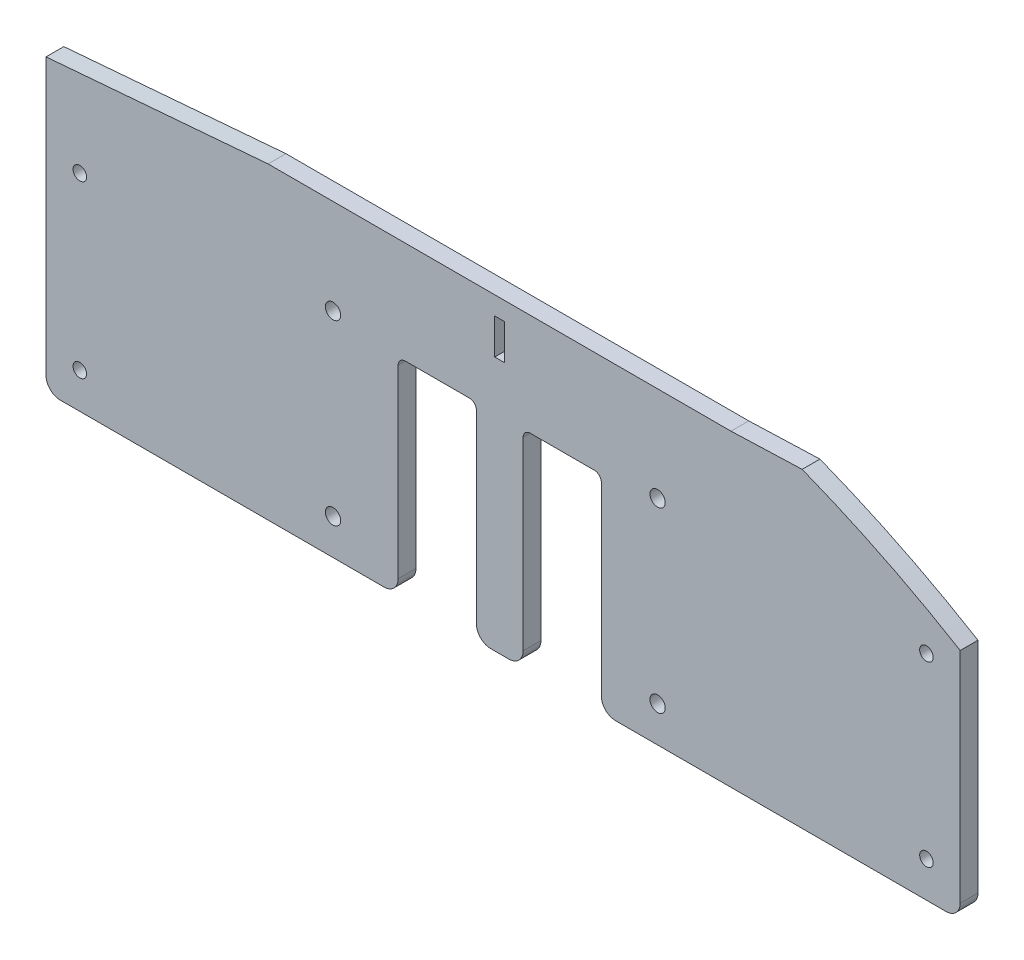
SolidWorks part; units mm, degrees
ref_plane "Front Plane" through (0, 0, 0) normal (0, 0, 1) x (1, 0, 0)
ref_plane "Top Plane" through (0, 0, 0) normal (0, 1, 0) x (1, 0, 0)
ref_plane "Right Plane" through (0, 0, 0) normal (1, 0, 0) x (0, 0, -1)
sketch "Sketch1" plane through (0, 0, 0) normal (0, 0, 1) x (1, 0, 0)
  line L0 (-247.5, -213.0845) -> (-247.5, -198.9021) construction
  line L1 (-243.5, -252.9723) -> (-152.4982, -252.9723)
  line L2 (-247.5, -248.9723) -> (-247.5, -171.4071)
  line L3 (-164.4304, -152.9723) -> (-121.35, -152.9723)
  line L4 (9.5, -248.9723) -> (9.5, -187.4329)
  line L6 (-120, -252.1255) -> (-120, -249.5403) construction
  line L8 (-93.3778, -194.9705) -> (-111.3778, -194.9705)
  line L9 (-91.3778, -196.9705) -> (-91.3778, -248.9723)
  line L11 (-113.3778, -196.9705) -> (-113.3778, -248.9723)
  line L12 (-122.4982, -252.9723) -> (-117.3778, -252.9723)
  line L13 (-128.4982, -194.9705) -> (-146.4982, -194.9705)
  line L14 (-126.4982, -196.9705) -> (-126.4982, -248.9723)
  line L16 (-148.4982, -196.9705) -> (-148.4982, -248.9723)
  line L17 (-87.3778, -252.9723) -> (5.5, -252.9723)
  line L21 (0, -187.4329) -> (0, -185.3896) construction
  line L22 (-105, -258.3454) -> (-105, -242.9215) construction
  line L25 (-118.65, -171.4071) -> (-118.65, -181.4071)
  line L26 (-118.65, -181.4071) -> (-121.35, -181.4071)
  line L27 (-121.35, -181.4071) -> (-121.35, -171.4071)
  line L28 (-121.35, -171.4071) -> (-118.65, -171.4071)
  line L29 (-118.65, -152.9723) -> (-118.65, -162.9723)
  line L30 (-118.65, -162.9723) -> (-121.35, -162.9723)
  line L31 (-121.35, -162.9723) -> (-121.35, -152.9723)
  line L33 (-118.65, -152.9723) -> (-75.5696, -152.9723)
  arc A0 (5.5, -252.9723) -> (9.5, -248.9723) centre (5.5, -248.9723) ccw
  arc A1 (-243.5, -252.9723) -> (-247.5, -248.9723) centre (-243.5, -248.9723) cw
  arc A2 (-152.4982, -252.9723) -> (-148.4982, -248.9723) centre (-152.4982, -248.9723) ccw
  arc A3 (-126.4982, -248.9723) -> (-122.4982, -252.9723) centre (-122.4982, -248.9723) ccw
  arc A4 (-117.3778, -252.9723) -> (-113.3778, -248.9723) centre (-117.3778, -248.9723) ccw
  arc A5 (-91.3778, -248.9723) -> (-87.3778, -252.9723) centre (-87.3778, -248.9723) ccw
  arc A6 (-93.3778, -194.9705) -> (-91.3778, -196.9705) centre (-93.3778, -196.9705) cw
  arc A7 (-111.3778, -194.9705) -> (-113.3778, -196.9705) centre (-111.3778, -196.9705) ccw
  arc A8 (-128.4982, -194.9705) -> (-126.4982, -196.9705) centre (-128.4982, -196.9705) cw
  arc A9 (-146.4982, -194.9705) -> (-148.4982, -196.9705) centre (-146.4982, -196.9705) ccw
  circle A10 centre (0, -192.9215) radius 1.9
  circle A11 centre (0, -242.9215) radius 1.9
  circle A12 centre (-237.9938, -242.9215) radius 1.9
  circle A13 centre (-237.9938, -194.9705) radius 1.9
  circle A14 centre (-166.8154, -192.9215) radius 2.15
  circle A15 centre (-166.8154, -242.9215) radius 2.15
  circle A16 centre (-75.5696, -192.9215) radius 2.15
  circle A17 centre (-75.5696, -242.9215) radius 2.15
  spline S0 degree 2 poles (-75.5696, -152.9723) (-30.2789, -163.4977) (9.5, -187.4329) knots 0 0 0 1 1 1
  spline S1 degree 2 poles (-164.4304, -152.9723) (-207.7942, -154.1347) (-247.5, -171.4071) knots 0 0 0 1 1 1
  point P28 (-113.3778, -252.9723)
  point P64 (-208.9717, -158.6372)
  point P67 (0, 0)
  point P70 (0, 0)
  point P72 (0, 0)
  point P74 (-237.9938, -194.9705)
  point P75 (-237.9938, -242.9215)
extrude "Boss-Extrude1" add sketch "Sketch1" along normal blind 5
sketch "Sketch2" plane through (0, 0, 0) normal (0, 0, -1) x (-1, 0, 0)
  line L1 (120, -171.4071) -> (120, -142.6322) construction
  line L2 (247.5, -171.4071) -> (185.0584, -166.2552)
  line L3 (113.3262, -148.8572) -> (126.6738, -148.8572)
  line L5 (110.1946, -162.6322) -> (152.1946, -162.6322) construction
  line L6 (110.1946, -162.6322) -> (110.1946, -140.6322) construction
  line L7 (110.1946, -140.6322) -> (152.1946, -140.6322) construction
  line L8 (150.1946, -142.6322) -> (112.1946, -142.6322) construction
  line L9 (112.1946, -142.6322) -> (112.1946, -160.6322) construction
  line L10 (112.1946, -160.6322) -> (150.1946, -160.6322) construction
  line L11 (150.1946, -160.6322) -> (150.1946, -142.6322) construction
  line L12 (152.1946, -162.6322) -> (152.1946, -140.6322) construction
  line L13 (185.0584, -166.2552) -> (54.9432, -166.2552)
  line L15 (34.9282, -165.548) -> (54.9432, -166.2552)
  parabola Q1 (-9.5, -187.4329) -> (75.5696, -152.9723) focus (85.5102, -301.764) apex (30.2864, -167.4093) construction
  parabola Q2 (164.4304, -152.9723) -> (247.5, -171.4071) focus (183.6652, -265.2453) apex (207.9263, -158.3972) construction
  spline S0 degree 2 poles (58.3159, -155.8012) (63.4247, -156.0716) (70.6543, -151.7415) knots 0 0 0 0.409142 0.409142 0.409142
  spline S1 degree 2 poles (185.5971, -153.3849) (156.5631, -146.9284) (126.6738, -148.8572) knots 0 0 0 1 1 1
  spline S2 degree 2 poles (185.5971, -153.3849) (219.1382, -148.7521) (247.5, -171.4071) knots 0 0 0 1 1 1
  spline S3 degree 2 poles (58.3159, -155.8012) (45.8933, -158.7544) (34.9282, -165.548) knots 0 0 0 1 1 1
  spline S4 degree 2 poles (113.3262, -148.8572) (91.8865, -148.6649) (70.6543, -151.7415) knots 0 0 0 1 1 1
  point P10 (198.8953, -154.7009)
  point P12 (0, 0)
  point P14 (120, -148.8572)
  point P15 (247.5, -171.4071)
  point P30 (0, 0)
  point P31 (0, 0)
  point P36 (185.5971, -153.3849)
  point P38 (203.8532, -152.9187)
  spline M15 degree 2 poles (247.5, -171.4071) (207.7942, -154.1347) (164.4304, -152.9723) knots 0 0 0 1 1 1
  line M16 (164.4304, -152.9723) -> (121.35, -152.9723)
  line M17 (121.35, -152.9723) -> (121.35, -162.9723)
  line M19 (118.65, -162.9723) -> (118.65, -152.9723)
  line M20 (118.65, -152.9723) -> (75.5696, -152.9723)
  dimension "D1" = 2
  dimension "D2" = 2
  dimension "D3" = 2
  dimension "D4" = 2
extrude "Boss-Extrude2" add sketch "Sketch2" against normal blind 5
extrude "Cut-Extrude1" cut sketch "Sketch2<2>" against normal blind 5 contours L12 L7 L6 L5 M16 M20 M19 M17 | L5 L12 M16 M17 | L6 L5 M19 M20 | S2 M15 region at (-140.7389, -159.2141, 0)
sketch "Sketch2<2>" plane through (0, 0, 0) normal (0, 0, -1) x (-1, 0, 0) same geometry as "Sketch2"
